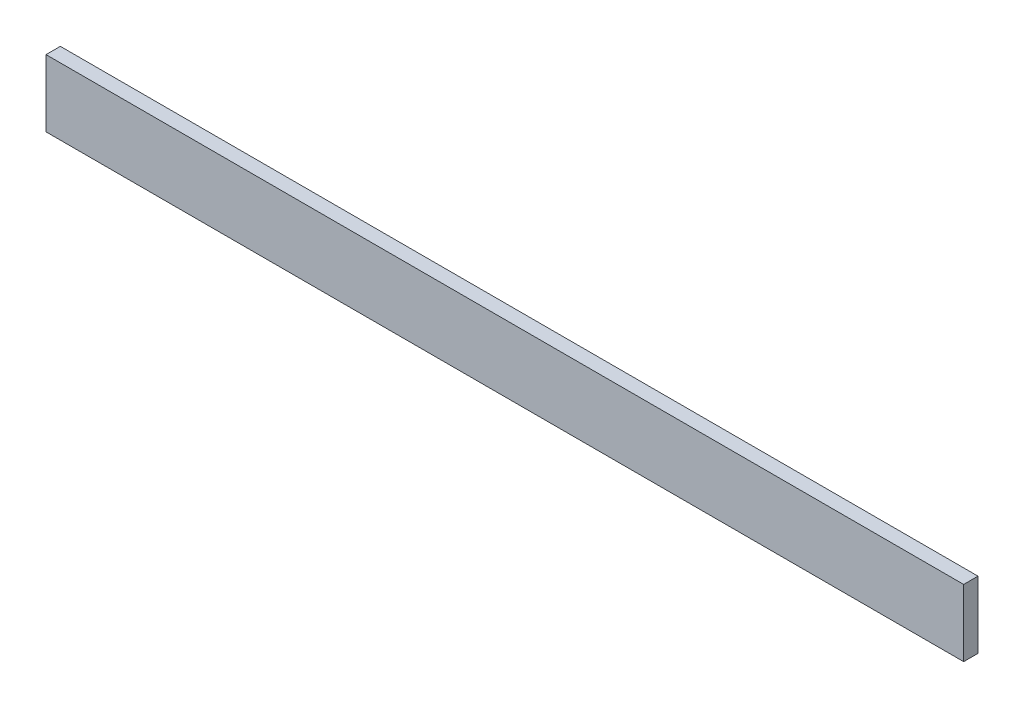
SolidWorks part; units mm, degrees
material "Cedar"
ref_plane "Front Plane" through (0, 0, 0) normal (0, 0, 1) x (1, 0, 0)
ref_plane "Top Plane" through (0, 0, 0) normal (0, 1, 0) x (1, 0, 0)
ref_plane "Right Plane" through (0, 0, 0) normal (1, 0, 0) x (0, 0, -1)
sketch "Sketch1" plane through (0, 0, 0) normal (1, 0, 0) x (0, 0, -1)
  line L1 (-9.525, -44.45) -> (9.525, -44.45)
  line L2 (-9.525, -44.45) -> (-9.525, 44.45)
  line L3 (-9.525, 44.45) -> (9.525, 44.45)
  line L4 (9.525, -44.45) -> (9.525, 44.45)
  line L5 (-9.525, -44.45) -> (9.525, 44.45) construction
  line L6 (-9.525, 44.45) -> (9.525, -44.45) construction
  point P0 (0, 0)
  dimension "D1" = 88.9
  dimension "D2" = 19.05
extrude "Boss-Extrude1" add sketch "Sketch1" along normal blind 609.6 and the other way blind 609.6
